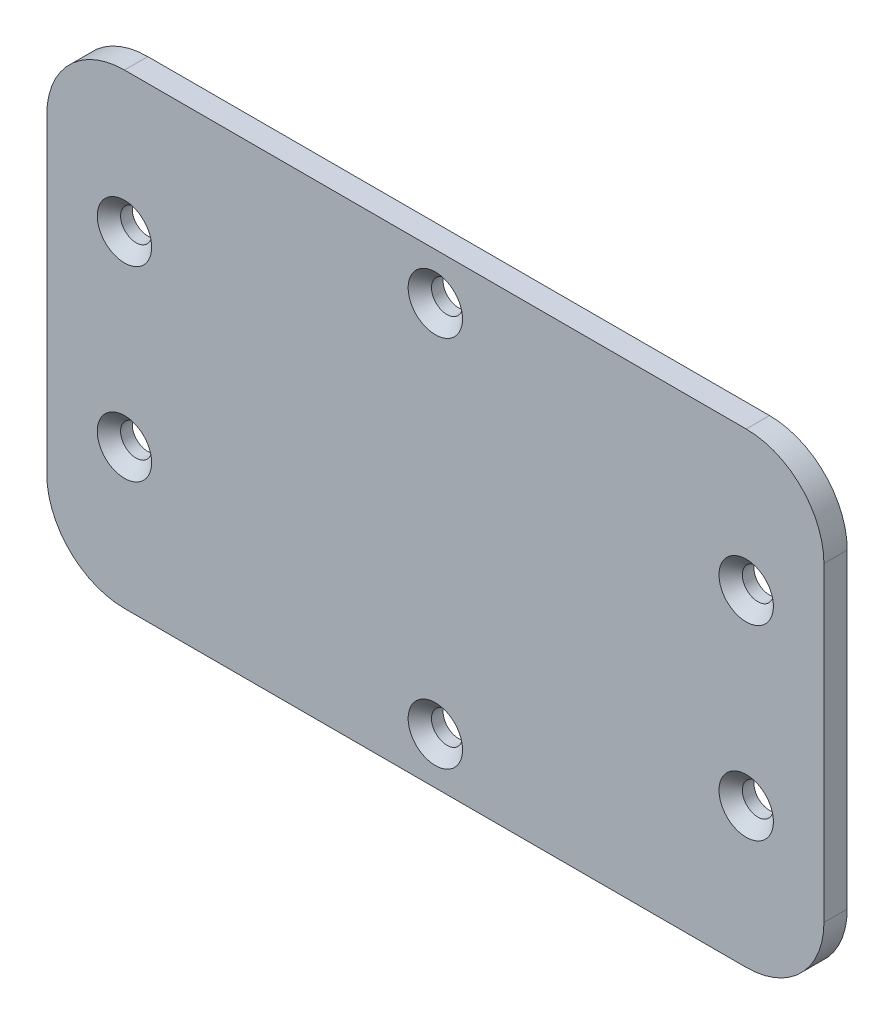
SolidWorks part; units mm, degrees
ref_plane "Ebene vorne" through (0, 0, 0) normal (0, 0, 1) x (1, 0, 0)
ref_plane "Ebene oben" through (0, 0, 0) normal (0, 1, 0) x (1, 0, 0)
ref_plane "Ebene rechts" through (0, 0, 0) normal (1, 0, 0) x (0, 0, -1)
sketch "Skizze1" plane through (0, 0, 0) normal (0, 0, 1) x (1, 0, 0)
  line L0 (-25, 0) -> (25, 0) construction
  line L1 (-25, 15) -> (25, 15)
  line L2 (-25, 15) -> (-25, -15)
  line L3 (-25, -15) -> (25, -15)
  line L4 (25, 15) -> (25, -15)
  dimension "D1" = 30
  dimension "D2" = 50
base flange "Basis-Blech1" sketch "Skizze1" thickness 1.5 reverse thickness direction no parameters "D1"=2.5
fillet "Verrundung1" radius 5 4 edges at (25, 15, -0.75) (25, -15, -0.75) (-25, -15, -0.75) (-25, 15, -0.75)
hole_wizard "Formsenkung für M3 Senkschraube mit Innensechskant2" positions "Skizze9" profile "Skizze10" countersink size "M3" standard "DIN"
sketch "Skizze9" plane through (-12.3085, 4.9028, 0) normal (0, 0, -1) x (-1, 0, 0)
  line L2 (7.6915, 1.0972) -> (-32.3085, 1.0972) construction
  line L6 (-12.3085, 7.0972) -> (-12.3085, 1.0972) construction
  line L7 (-12.3085, 1.0972) -> (-12.3085, -4.9028) construction
  line L8 (-12.3085, -4.9028) -> (-12.3085, -10.9028) construction
  line L9 (-12.3085, -10.9028) -> (-12.3085, -16.9028) construction
  line L11 (-32.3085, -10.9028) -> (7.6915, -10.9028) construction
  point P0 (-32.3085, 1.0972)
  point P2 (-12.3085, 7.0972)
  point P4 (7.6915, 1.0972)
  point P6 (7.6915, -10.9028)
  point P8 (-12.3085, -16.9028)
  point P10 (-32.3085, -10.9028)
sketch "Skizze10" plane through (20, 6, 0) normal (1, 0, 0) x (0, -1, 0)
  line L0 (0, 0) -> (0, 8.4807)
  line L1 (0, 8.4807) -> (0.8, 8)
  line L2 (0.8, 8) -> (0.8, 0.95)
  line L3 (0.8, 0.95) -> (1.75, 0)
  line L4 (1.75, 0) -> (0, 0)
  line L5 (-0.8, 0.95) -> (-1.75, 0) construction
  line L6 (0, 8.4807) -> (-0.8, 8) construction
  line L7 (0, -6.35) -> (0, 107.95) construction
  dimension "Bohrerdurchmesser" = 1.6
  dimension "Bohrungstiefe" = 8
  dimension "Senkdurchmesser (Oben)" = 3.5
  dimension "Senkwinkel (Oben)" = 90
  dimension "Spitzenwinkel" = 118
sketch "Skizze8" plane through (0, 0, -1.5) normal (0, 0, -1) x (-1, 0, 0)
  circle A0 centre (-20, 6) radius 1
  circle A1 centre (0, 12) radius 1
  circle A2 centre (20, 6) radius 1
  circle A3 centre (20, -6) radius 1
  circle A4 centre (0, -12) radius 1
  circle A5 centre (-20, -6) radius 1
  dimension "D1" = 2
extrude "Schnitt-Linear austragen1" cut sketch "Skizze8" against normal through all normal cut yes
sketch "Biegung-Linien1" [suppressed] plane through (0, 0, 0) normal (0, 1, 0) x (1, 0, 0)
sketch "Rahmen1" [suppressed] plane through (0, 0, 0) normal (0, 1, 0) x (1, 0, 0)
sheet metal parameters "Blech(1)" thickness 1.5 parameters "D1"=2.5
flat pattern "Abwicklung(1)" [suppressed]
sketch "Biegung-Linien2" plane through (0, 0, 0) normal (0, 1, 0) x (1, 0, 0)
sketch "Rahmen2" [suppressed] plane through (0, 0, 0) normal (0, 1, 0) x (1, 0, 0)
sheet metal parameters "Blech(3)" thickness 1.5 parameters "D1"=2.5
flat pattern "Abwicklung(1)"
sketch "Biegung-Linien2" plane through (0, 0, 0) normal (0, 1, 0) x (1, 0, 0)
sketch3d "Rahmen2" [suppressed]
  line L0 (-25, 15, 0) -> (25, 15, 0) construction
  line L1 (-25, -15, 0) -> (25, -15, 0) construction
  line L2 (-25, 15, 0) -> (-25, -15, 0) construction
  line L3 (25, 15, 0) -> (25, -15, 0) construction
sheet metal parameters "Blech(4)" thickness 1.5 parameters "D1"=2.5
flat pattern "Abwicklung(1)"
sketch "Biegung-Linien2" plane through (0, 0, 0) normal (0, 1, 0) x (1, 0, 0)
sketch3d "Rahmen2" [suppressed]
  line L0 (-25, 15, 0) -> (25, 15, 0) construction
  line L1 (-25, -15, 0) -> (25, -15, 0) construction
  line L2 (-25, 15, 0) -> (-25, -15, 0) construction
  line L3 (25, 15, 0) -> (25, -15, 0) construction
